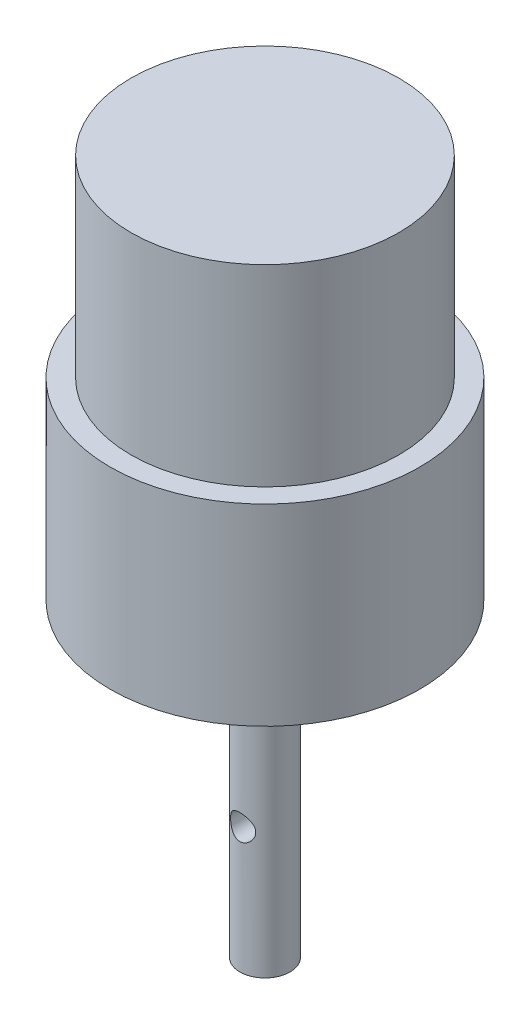
SolidWorks part; units mm, degrees
ref_plane "Front Plane" through (0, 0, 0) normal (0, 0, 1) x (1, 0, 0)
ref_plane "Top Plane" through (0, 0, 0) normal (0, 1, 0) x (1, 0, 0)
ref_plane "Right Plane" through (0, 0, 0) normal (1, 0, 0) x (0, 0, -1)
sketch "Sketch2" plane through (0, 0, 0) normal (0, 1, 0) x (1, 0, 0)
  circle A0 centre (0, 0) radius 18.5
  dimension "D1" = 37
extrude "Boss-Extrude1" add sketch "Sketch2" along normal blind 23 contours A0
sketch "Sketch3" plane through (0, 23, 0) normal (0, 1, 0) x (1, 0, 0)
  circle A0 centre (0, 0) radius 16
extrude "Boss-Extrude2" add sketch "Sketch3" along normal blind 23 contours A0
sketch "Sketch4" plane through (0, 0, 0) normal (0, -1, 0) x (1, 0, 0)
  circle A0 centre (0, 0) radius 7
  dimension "D1" = 14
extrude "Boss-Extrude3" add sketch "Sketch4" along normal blind 8 contours A0
sketch "Sketch5" plane through (0, 0, 0) normal (0, 1, 0) x (1, 0, 0)
  circle A0 centre (0, 0) radius 3
sketch "Sketch6" plane through (0, 46, 0) normal (0, 1, 0) x (1, 0, 0)
  circle A0 centre (0, 0) radius 3
sketch "Sketch7" plane through (0, 0, 0) normal (0, 0, 1) x (1, 0, 0)
  line L0 (0, 0) -> (0, -22)
  circle A0 centre (0, -22) radius 1.5
sketch "Sketch12" plane through (0, 0, 0) normal (0, 1, 0) x (1, 0, 0)
  circle A0 centre (0, 0) radius 3
extrude "Boss-Extrude6" add sketch "Sketch12" against normal blind 37
extrude "Cut-Extrude1" cut sketch "Sketch7" against normal blind 10 and the other way blind 10 contours A0
